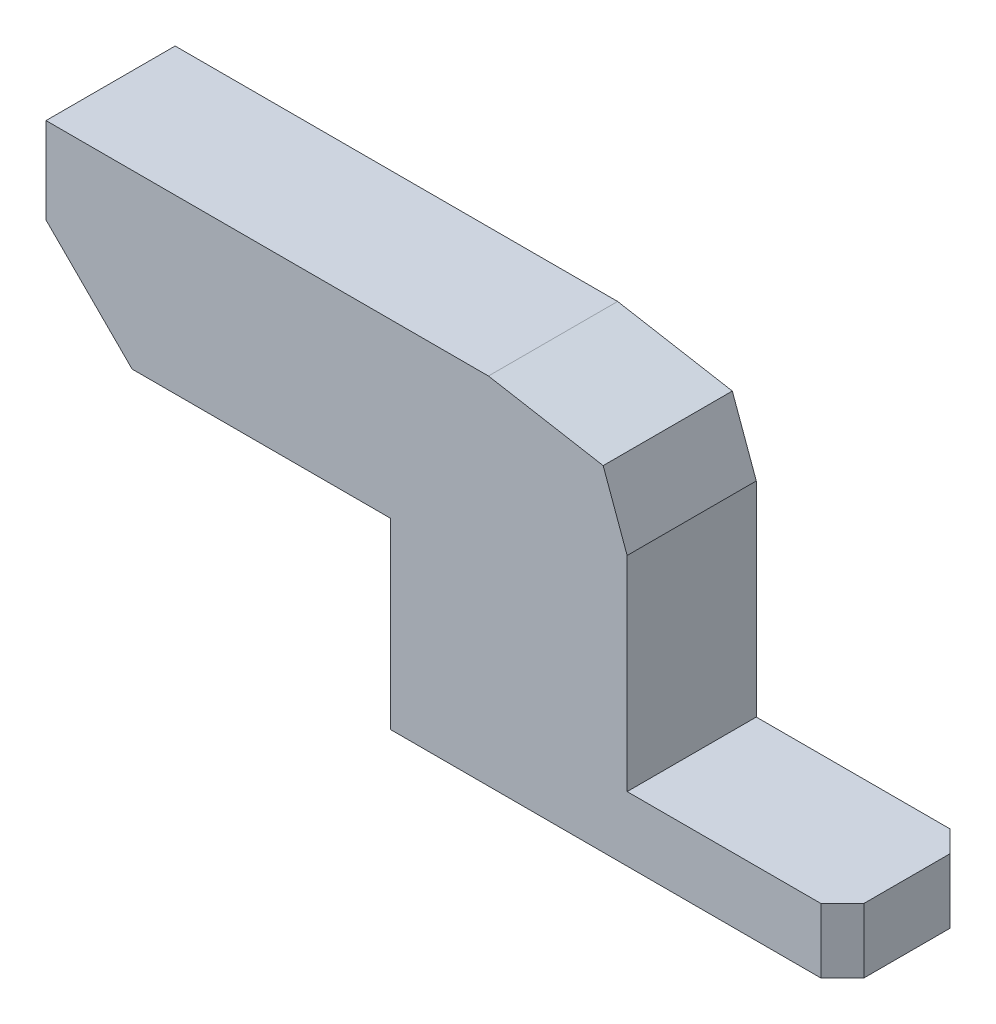
SolidWorks part; units mm, degrees
material "3D printed plastic"
ref_plane "Front Plane" through (0, 0, 0) normal (0, 0, 1) x (1, 0, 0)
ref_plane "Top Plane" through (0, 0, 0) normal (0, 1, 0) x (1, 0, 0)
ref_plane "Right Plane" through (0, 0, 0) normal (1, 0, 0) x (0, 0, -1)
sketch "Sketch1" plane through (0, 0, 0) normal (0, 0, 1) x (1, 0, 0)
  line L0 (16, 0) -> (37, 0)
  line L1 (37, 0) -> (37, 3)
  line L2 (37, 3) -> (27, 3)
  line L3 (27, 3) -> (27, 12.5)
  line L4 (27, 12.5) -> (25.5441, 16.5)
  line L5 (25.5441, 16.5) -> (0, 16.5)
  line L6 (0, 16.5) -> (0, 8.5)
  line L7 (0, 8.5) -> (0, 0) construction
  line L8 (0, 8.5) -> (16, 8.5)
  line L9 (0, 0) -> (16, 0) construction
  line L11 (16, 8.5) -> (16, 0)
  dimension "D1" = 4
  dimension "D2" = 20
  dimension "D3" = 27
  dimension "D4" = 13.5
  dimension "D5" = 3
  dimension "D6" = 10
  dimension "D7" = 16
  dimension "D8" = 8
extrude "Boss-Extrude1" add sketch "Sketch1" along normal mid plane 6
chamfer "Chamfer1" distance 1 angle 45 2 edges at (37, 1.5, -3) (37, 1.5, 3)
chamfer "Chamfer3" distance 1 angle 60 1 edges at (25.5441, 16.5, 0) first distance on face at (26.2721, 14.5, 0)
sketch "Sketch2" plane through (0, 0, 0) normal (0, -1, 0) x (1, 0, 0)
  line L0 (25, 0) -> (19, 0) construction
  line L1 (19, 0) -> (16, 0) construction
  line L2 (16, 3) -> (16, -3) construction
  circle A0 centre (19, 0) radius 1.25
  circle A1 centre (25, 0) radius 1.25
  dimension "D1" = 3
  dimension "D2" = 2.5
  dimension "D3" = 6
extrude "Cut-Extrude1" cut sketch "Sketch2" against normal blind 10
chamfer "Chamfer4" distance 4 angle 45 1 edges at (0, 8.5, 0)
